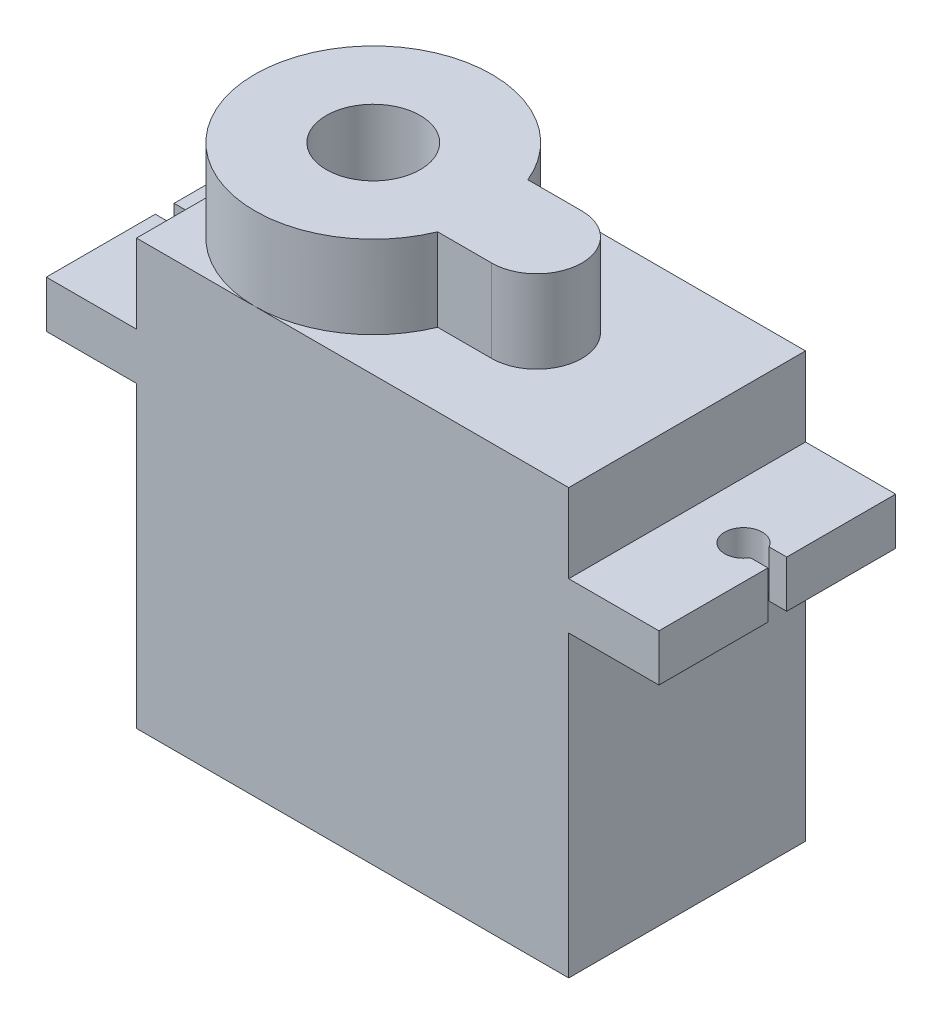
SolidWorks part; units mm, degrees
ref_plane "Alzado" through (0, 0, 0) normal (0, 0, 1) x (1, 0, 0)
ref_plane "Planta" through (0, 0, 0) normal (0, 1, 0) x (1, 0, 0)
ref_plane "Vista lateral" through (0, 0, 0) normal (1, 0, 0) x (0, 0, -1)
sketch "Croquis1" plane through (0, 0, 0) normal (0, 0, 1) x (1, 0, 0)
  line L0 (11.5, 0) -> (-11.5, 0)
  line L1 (-11.5, 0) -> (-11.5, 15.9)
  line L2 (-11.5, 15.9) -> (-16.3, 15.9)
  line L3 (-16.3, 15.9) -> (-16.3, 18.4)
  line L4 (-16.3, 18.4) -> (-11.5, 18.4)
  line L5 (-11.5, 18.4) -> (-11.5, 22.6)
  line L6 (-11.5, 22.6) -> (11.5, 22.6)
  line L8 (0, 35.0828) -> (0, -5.7212) construction
  line L9 (11.5, 0) -> (11.5, 15.9)
  line L10 (11.5, 15.9) -> (16.3, 15.9)
  line L11 (16.3, 15.9) -> (16.3, 18.4)
  line L12 (16.3, 18.4) -> (11.5, 18.4)
  line L13 (11.5, 18.4) -> (11.5, 22.6)
  dimension "D1" = 23
  dimension "D2" = 15.9
  dimension "D3" = 2.5
  dimension "D4" = 4.2
  dimension "D5" = 4.8
  dimension "D6" = 4.8
extrude "Saliente-Extruir1" add sketch "Croquis1" along normal blind 12.6 contours L1 L2 L3 L4 L5 L6 L13 L12 L11 L10 L9 L0
sketch "Croquis2" plane through (0, 18.4, 0) normal (0, 1, 0) x (1, 0, 0)
  line L0 (-16.3, -12.6) -> (-16.3, -6.8) construction
  line L1 (-16.3, -12.6) -> (-16.3, 0) construction
  line L2 (-16.3, -6.3) -> (16.3, -6.3) construction
  line L3 (16.3, -12.6) -> (16.3, 0) construction
  line L4 (-16.3, 0) -> (-16.3, -5.8) construction
  line L5 (-16.3, -6.8) -> (-15.366, -6.8)
  line L6 (-16.3, -5.8) -> (-15.366, -5.8)
  line L7 (0, 0) -> (0, -12.6) construction
  line L8 (-11.5, -12.6) -> (11.5, -12.6) construction
  line L9 (-16.3, -6.8) -> (-16.3, -5.8)
  line L10 (-15.366, -5.8) -> (-15.366, -6.8)
  line L11 (15.366, -5.8) -> (15.366, -6.8)
  line L12 (16.3, -5.8) -> (15.366, -5.8)
  line L13 (16.3, -6.8) -> (16.3, -5.8)
  line L14 (16.3, -6.8) -> (15.366, -6.8)
  line L15 (-13.5, -6.3) -> (-13.5, -4.3984) construction
  line L16 (-11.503, -6.3) -> (-11.5, -4.3984) construction
  line L17 (-11.5, -12.6) -> (-11.5, 0) construction
  circle A0 centre (-14.5, -6.3) radius 1
  circle A1 centre (14.5, -6.3) radius 1
  point P12 (-14.5, -6.3)
  dimension "D4" = 1
  dimension "D1" = 5.8
  dimension "D2" = 2
  dimension "D3" = 1.8
extrude "Cortar-Extruir2" cut sketch "Croquis2" against normal blind 2.5 contours A1 L14 L12 | L11 A1 | L11 A1 | L5 A0 L6 L9 | A0 L10 | A0 L10 region at (-15.8774, 18.4, 6.3) region at (-15.4199, 18.4, 6.3) region at (-14.4727, 18.4, 6.3) region at (15.4199, 18.4, 6.3) region at (15.8774, 18.4, 6.3) region at (14.4727, 18.4, 6.3)
sketch "Croquis4" plane through (0, 22.6, 0) normal (0, 1, 0) x (1, 0, 0)
  line L0 (-11.5, -6.3) -> (-5.2, -6.3) construction
  line L1 (-11.5, -12.6) -> (-11.5, 0) construction
  line L2 (-5.2, -6.3) -> (3.5, -6.3) construction
  line L4 (-1.3, -8.7) -> (3.5, -8.7)
  line L5 (-1.3, -8.7) -> (-1.3, -3.9)
  line L6 (-1.3, -3.9) -> (3.5, -3.9)
  line L7 (3.5, -8.7) -> (3.5, -3.9)
  line L8 (-1.3, -8.7) -> (3.5, -3.9) construction
  line L9 (-1.3, -3.9) -> (3.5, -8.7) construction
  circle A0 centre (-5.2, -6.3) radius 6.3
  circle A1 centre (3.5, -6.3) radius 2.4
  circle A2 centre (-5.2, -6.3) radius 2.5
  point P7 (1.1, -6.3)
  point P8 (1.1, -6.3)
  dimension "D2" = 12.6
  dimension "D4" = 4.8
  dimension "D5" = 5
  dimension "D1" = 6.3
  dimension "D3" = 8.7
extrude "Saliente-Extruir4" add sketch "Croquis4" along normal blind 4.4 contours A0 L4 L5 L6 A2 | L7 A1 | L7 A1 | A1 A0 L4 | A1 L6 A0 | L4 A0 L6 L5 region at (-0.1735, 22.6, 6.3) region at (-0.3375, 22.6, 8.8749) region at (1.4786, 22.6, 8.1501) region at (2.4814, 22.6, 6.3) region at (4.5186, 22.6, 6.3) region at (1.4786, 22.6, 4.4499)
